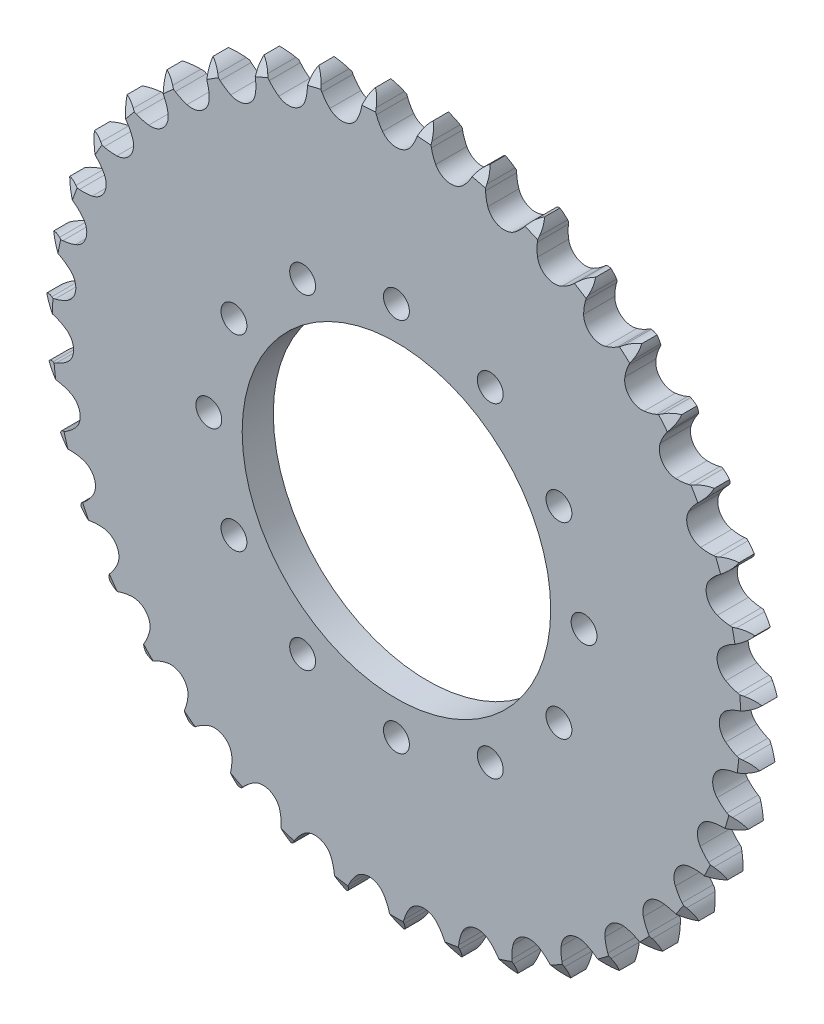
SolidWorks part; units mm, degrees
material "7075-T6 (SN)"
ref_plane "Front Plane" through (0, 0, 0) normal (0, 0, 1) x (1, 0, 0)
ref_plane "Top Plane" through (0, 0, 0) normal (0, 1, 0) x (1, 0, 0)
ref_plane "Right Plane" through (0, 0, 0) normal (1, 0, 0) x (0, 0, -1)
sketch "Work Sketch" plane through (0, 0, 0) normal (0, 0, 1) x (1, 0, 0)
  line L0 (0, 0) -> (0, 160.4542) construction
  line L1 (-112.0919, 78.9148) -> (87.2579, 78.9148) construction
  line L2 (5.102, 120.8822) -> (5.102, 112.9699) construction
  line L3 (-12.8497, 82.6953) -> (16.7256, 82.6953) construction
  line L4 (5.102, 82.6953) -> (-6.0879, 74.4036) construction
  line L5 (5.102, 82.6953) -> (-4.6505, 79.1506) construction
  line L6 (-4.6505, 79.1506) -> (-6.8863, 85.3019)
  line L7 (-11.5114, 78.0206) -> (-7.1525, 78.0206) construction
  line L8 (-11.0765, 124.7602) -> (-11.0765, 110.2345) construction
  line L9 (0, 0) -> (-3.4402, 42.6146) construction
  circle A0 centre (0, 0) radius 78.9148
  circle A1 centre (0, 78.9148) radius 4.0088
  arc A2 (-4.6505, 79.1506) -> (-3.2209, 76.5281) centre (5.0804, 82.7541) ccw
  circle A3 centre (-11.0765, 78.0206) radius 6.4254
  point P23 (-3.2209, 76.5281)
  dimension "D1" = 157.8295
  dimension "D8" = 10.3767
  dimension "D2" = 8.0177
  dimension "D3" = 5.102
  dimension "D4" = 3.7806
  dimension "D5" = 36.538
  dimension "D6" = 16.564
  dimension "D7" = 10.3767
  dimension "D9" = 0.8942
  dimension "D10" = 11.0765
  dimension "D11" = 4.615
sketch "Teeth Sketch" plane through (0, 0, 0) normal (0, 0, 1) x (1, 0, 0)
  line L0 (5.0376, 80.2155) -> (4.6505, 79.1506)
  line L1 (-7.4865, 92.7372) -> (-4.7839, 59.2593) construction
  line L2 (0, 0) -> (-10.9133, 132.3061) construction
  line L3 (7.8951, 79.9848) -> (8.1063, 78.8717)
  line L4 (16093.3137, -199351.4616) -> (-16096.7539, 199394.0762) construction
  line L5 (0, 146.3285) -> (0, 56.9858) construction
  line L6 (17.8398, 78.3686) -> (17.287, 77.3797)
  line L7 (0, -200000) -> (0, 200160.4542) construction
  line L8 (20.6234, 77.6826) -> (20.6533, 76.5499)
  line L9 (-4.6505, 79.1506) -> (-6.8863, 85.3019) construction
  line L10 (44.1616, 67.154) -> (43.8313, 66.0702)
  line L11 (-5.0376, 80.2155) -> (-4.6505, 79.1506)
  line L12 (30.18, 74.4921) -> (29.4757, 73.6046)
  line L13 (32.8175, 73.3684) -> (32.6653, 72.2456)
  line L14 (41.7385, 68.6862) -> (40.901, 67.9232)
  line L15 (52.2161, 61.1014) -> (51.267, 60.4826)
  line L16 (54.362, 59.2003) -> (53.8621, 58.1836)
  line L17 (61.3413, 51.9341) -> (60.3052, 51.4756)
  line L18 (63.1544, 49.7134) -> (62.4979, 48.79)
  line L19 (68.8777, 41.4218) -> (67.7815, 41.1354)
  line L20 (70.3112, 38.939) -> (69.515, 38.1328)
  line L21 (74.6303, 29.8366) -> (73.5023, 29.7298)
  line L22 (75.6469, 27.156) -> (74.7318, 26.488)
  line L23 (78.45, 17.4787) -> (77.3195, 17.5542)
  line L24 (79.0234, 14.6698) -> (78.013, 14.1572)
  line L25 (80.2378, 4.6681) -> (79.1341, 4.9239)
  line L26 (80.3533, 1.8035) -> (79.2737, 1.4597)
  line L27 (79.9476, -8.2634) -> (78.8992, -7.8338)
  line L28 (79.602, -11.1094) -> (78.4813, -11.2756)
  line L29 (77.5867, -20.9809) -> (76.6208, -20.3887)
  line L30 (76.7891, -23.7346) -> (75.6562, -23.7189)
  line L31 (73.2164, -33.155) -> (72.358, -32.4155)
  line L32 (71.9874, -35.7451) -> (70.8717, -35.5478)
  line L33 (66.9499, -44.4704) -> (66.2212, -43.6028)
  line L34 (65.3213, -46.8298) -> (64.2517, -46.4561)
  line L35 (58.9493, -54.634) -> (58.3693, -53.6608)
  line L36 (56.9634, -56.7016) -> (55.9676, -56.1612)
  line L37 (49.422, -63.3827) -> (49.0056, -62.329)
  line L38 (47.1301, -65.1049) -> (46.2339, -64.4118)
  line L39 (38.6147, -70.4897) -> (38.3727, -69.3829)
  line L40 (36.0763, -71.822) -> (35.3028, -70.9941)
  line L41 (26.8073, -75.7712) -> (26.746, -74.6398)
  line L42 (24.088, -76.679) -> (23.4574, -75.7377)
  line L43 (14.3056, -79.0901) -> (14.4266, -77.9636)
  line L44 (11.4759, -79.55) -> (11.0044, -78.5198)
  line L45 (1.4334, -80.3607) -> (1.7335, -79.2682)
  line L46 (-1.4334, -80.3607) -> (-1.7335, -79.2682)
  line L47 (-11.4759, -79.55) -> (-11.0044, -78.5198)
  line L48 (-14.3056, -79.0901) -> (-14.4266, -77.9636)
  line L49 (-24.088, -76.679) -> (-23.4574, -75.7377)
  line L50 (-26.8073, -75.7712) -> (-26.746, -74.6398)
  line L51 (-36.0763, -71.822) -> (-35.3028, -70.9941)
  line L52 (-38.6147, -70.4897) -> (-38.3727, -69.3829)
  line L53 (-47.1301, -65.1049) -> (-46.2339, -64.4118)
  line L54 (-49.422, -63.3827) -> (-49.0056, -62.329)
  line L55 (-56.9634, -56.7016) -> (-55.9676, -56.1612)
  line L56 (-58.9493, -54.634) -> (-58.3693, -53.6608)
  line L57 (-65.3213, -46.8298) -> (-64.2517, -46.4561)
  line L58 (-66.9499, -44.4704) -> (-66.2212, -43.6028)
  line L59 (-71.9874, -35.7451) -> (-70.8717, -35.5478)
  line L60 (-73.2164, -33.155) -> (-72.358, -32.4155)
  line L61 (-76.7891, -23.7346) -> (-75.6562, -23.7189)
  line L62 (-77.5867, -20.9809) -> (-76.6208, -20.3887)
  line L63 (-79.602, -11.1094) -> (-78.4813, -11.2756)
  line L64 (-79.9476, -8.2634) -> (-78.8992, -7.8338)
  line L65 (-80.3533, 1.8035) -> (-79.2737, 1.4597)
  line L66 (-80.2378, 4.6681) -> (-79.1341, 4.9239)
  line L67 (-79.0234, 14.6698) -> (-78.013, 14.1572)
  line L68 (-78.45, 17.4787) -> (-77.3195, 17.5542)
  line L69 (-75.6469, 27.156) -> (-74.7318, 26.488)
  line L70 (-74.6303, 29.8366) -> (-73.5023, 29.7298)
  line L71 (-70.3112, 38.939) -> (-69.515, 38.1328)
  line L72 (-68.8777, 41.4218) -> (-67.7815, 41.1354)
  line L73 (-63.1544, 49.7134) -> (-62.4979, 48.79)
  line L74 (-61.3413, 51.9341) -> (-60.3052, 51.4756)
  line L75 (-54.362, 59.2003) -> (-53.8621, 58.1836)
  line L76 (-52.2161, 61.1014) -> (-51.267, 60.4826)
  line L77 (-44.1616, 67.154) -> (-43.8313, 66.0702)
  line L78 (-41.7385, 68.6862) -> (-40.901, 67.9232)
  line L79 (-32.8175, 73.3684) -> (-32.6653, 72.2456)
  line L80 (-30.18, 74.4921) -> (-29.4757, 73.6046)
  line L81 (-20.6234, 77.6826) -> (-20.6533, 76.5499)
  line L82 (-17.8398, 78.3686) -> (-17.287, 77.3797)
  line L83 (-7.8951, 79.9848) -> (-8.1063, 78.8717)
  arc A0 (-6.8336, 82.8459) -> (-5.0376, 80.2155) centre (-11.0765, 78.0206) cw
  circle A1 centre (-11.0765, 78.0206) radius 6.4254 construction
  arc A2 (-3.2209, 76.5281) -> (-4.6505, 79.1506) centre (5.0804, 82.7541) cw
  arc A3 (-4.6505, 79.1506) -> (-3.2209, 76.5281) centre (5.0804, 82.7541) ccw construction
  circle A4 centre (0, 78.9148) radius 4.0088 construction
  arc A5 (-3.2209, 76.5281) -> (3.2209, 76.5281) centre (0, 78.9148) ccw
  arc A6 (3.2209, 76.5281) -> (4.6505, 79.1506) centre (-5.0804, 82.7541) ccw
  arc A7 (6.8336, 82.8459) -> (5.0376, 80.2155) centre (11.0765, 78.0206) ccw
  arc A8 (6.5443, 82.8692) -> (7.8951, 79.9848) centre (1.5824, 78.787) cw
  arc A9 (9.0967, 76.0537) -> (8.1063, 78.8717) centre (18.2893, 80.8676) cw
  arc A10 (9.0967, 76.0537) -> (15.4552, 75.0204) centre (12.6588, 77.8928) ccw
  arc A11 (15.4552, 75.0204) -> (17.287, 77.3797) centre (8.2601, 82.4975) ccw
  arc A12 (20.0345, 80.6769) -> (17.8398, 78.3686) centre (23.4484, 75.2334) ccw
  arc A13 (19.7528, 80.7463) -> (20.6234, 77.6826) centre (14.2002, 77.5129) cw
  arc A14 (21.1788, 73.6096) -> (20.6533, 76.5499) centre (31.0245, 76.8865) cw
  arc A15 (21.1788, 73.6096) -> (27.2892, 71.5697) centre (24.9898, 74.8535) ccw
  arc A16 (27.2892, 71.5697) -> (29.4757, 73.6046) centre (21.3867, 80.1041) ccw
  arc A17 (32.7165, 76.4184) -> (30.18, 74.4921) centre (35.2131, 70.4978) ccw
  arc A18 (32.4496, 76.5321) -> (32.8175, 73.3684) centre (26.4502, 74.2313) cw
  arc A19 (32.7124, 69.2591) -> (32.6653, 72.2456) centre (42.9562, 70.9142) cw
  arc A20 (32.7124, 69.2591) -> (38.4163, 66.2654) centre (36.6735, 69.8756) ccw
  arc A21 (38.4163, 66.2654) -> (40.901, 67.9232) centre (33.9593, 75.6361) ccw
  arc A22 (44.5512, 70.1807) -> (41.7385, 68.6862) centre (46.0657, 63.9363) ccw
  arc A23 (44.306, 70.3358) -> (44.1616, 67.154) centre (38.0153, 69.0271) cw
  arc A24 (43.3987, 63.1147) -> (43.8313, 66.0702) centre (53.7754, 63.1052) cw
  arc A25 (43.3987, 63.1147) -> (48.5486, 59.2448) centre (47.4074, 63.0878) ccw
  arc A26 (48.5486, 59.2448) -> (51.267, 60.4826) centre (45.6524, 69.2092) ccw
  arc A27 (55.2321, 62.1253) -> (52.2161, 61.1014) centre (55.7253, 55.7189) ccw
  arc A28 (55.0149, 62.3178) -> (54.362, 59.2003) centre (48.5957, 62.0351) cw
  arc A29 (52.961, 55.3358) -> (53.8621, 58.1836) centre (63.2018, 53.6618) cw
  arc A30 (52.961, 55.3358) -> (57.4234, 50.6899) centre (56.9135, 54.6662) ccw
  arc A31 (57.4234, 50.6899) -> (60.3052, 51.4756) centre (56.1632, 60.9898) ccw
  arc A32 (64.4824, 52.461) -> (61.3413, 51.9341) centre (63.9416, 46.0584) ccw
  arc A33 (64.2989, 52.6858) -> (63.1544, 49.7134) centre (57.9175, 53.4365) cw
  arc A34 (61.1517, 46.1237) -> (62.4979, 48.79) centre (70.9913, 42.8287) cw
  arc A35 (61.1517, 46.1237) -> (64.811, 40.8221) centre (64.9456, 44.8287) ccw
  arc A36 (64.811, 40.8221) -> (67.7815, 41.1354) centre (65.2193, 51.1908) ccw
  arc A37 (72.0627, 41.4379) -> (68.8777, 41.4218) centre (70.5018, 35.205) ccw
  arc A38 (71.9177, 41.6892) -> (70.3112, 38.939) centre (65.7393, 43.4539) cw
  arc A39 (67.7585, 35.717) -> (69.515, 38.1328) centre (76.9422, 30.8862) cw
  arc A40 (67.7585, 35.717) -> (70.5201, 29.8971) centre (71.2956, 33.8302) ccw
  arc A41 (70.5201, 29.8971) -> (73.5023, 29.7298) centre (72.5864, 40.0659) ccw
  arc A42 (77.7767, 29.3416) -> (74.6303, 29.8366) centre (75.2361, 23.4398) ccw
  arc A43 (77.6738, 29.6129) -> (75.6469, 27.156) centre (71.8585, 32.3458) cw
  arc A44 (72.6105, 24.3852) -> (74.7318, 26.488) centre (80.9003, 18.1439) cw
  arc A45 (72.6105, 24.3852) -> (74.4027, 18.1977) centre (75.7991, 21.9555) ccw
  arc A46 (74.4027, 18.1977) -> (77.3195, 17.5542) centre (78.0734, 27.9034) ccw
  arc A47 (81.4762, 16.4854) -> (78.45, 17.4787) centre (78.0218, 11.0675) ccw
  arc A48 (81.4182, 16.7697) -> (79.0234, 14.6698) centre (76.1166, 20.4) cw
  arc A49 (75.5818, 12.4219) -> (78.013, 14.1572) centre (82.7631, 4.9316) cw
  arc A50 (75.5818, 12.4219) -> (76.3583, 6.027) centre (78.3394, 9.5121) ccw
  arc A51 (76.3583, 6.027) -> (79.1341, 4.9239) centre (81.5384, 15.0182) ccw
  arc A52 (83.0656, 3.2022) -> (80.2378, 4.6681) centre (78.7868, -1.5914) ccw
  arc A53 (83.0539, 3.4922) -> (80.3533, 1.8035) centre (78.4033, 7.9259) cw
  arc A54 (76.5957, 0.1368) -> (79.2737, 1.4597) centre (82.4825, -8.4084) cw
  arc A55 (76.5957, 0.1368) -> (76.3363, -6.2998) centre (78.8508, -3.1776) ccw
  arc A56 (76.3363, -6.2998) -> (78.8992, -7.8338) centre (82.8916, 1.7441) ccw
  arc A57 (82.5035, -10.1639) -> (79.9476, -8.2634) centre (77.5113, -14.2091) ccw
  arc A58 (82.5385, -9.8758) -> (79.602, -11.1094) centre (78.6594, -4.7535) cw
  arc A59 (75.6257, -12.1517) -> (78.4813, -11.2756) centre (80.0655, -21.5307) cw
  arc A60 (75.6257, -12.1517) -> (74.3372, -18.4634) centre (77.3199, -15.785) ccw
  arc A61 (74.3372, -18.4634) -> (76.6208, -20.3887) centre (82.0979, -11.5753) ccw
  arc A62 (79.8047, -23.2668) -> (77.5867, -20.9809) centre (74.2283, -26.4587) ccw
  arc A63 (79.8855, -22.9881) -> (76.7891, -23.7346) centre (76.8783, -17.3098) cw
  arc A64 (72.6971, -24.1256) -> (75.6562, -23.7189) centre (75.5749, -34.0953) cw
  arc A65 (72.6971, -24.1256) -> (70.4128, -30.1488) centre (73.7866, -27.9836) ccw
  arc A66 (70.4128, -30.1488) -> (72.358, -32.4155) centre (79.178, -24.5948) ccw
  arc A67 (75.039, -35.7671) -> (73.2164, -33.155) centre (69.0227, -38.0232) ccw
  arc A68 (75.1634, -35.5049) -> (71.9874, -35.7451) centre (73.106, -29.4178) cw
  arc A69 (67.8857, -35.4746) -> (70.8717, -35.5478) centre (69.127, -45.7768) cw
  arc A70 (67.8857, -35.4746) -> (64.6648, -41.0534) centre (68.3422, -39.4574) ccw
  arc A71 (64.6648, -41.0534) -> (66.2212, -43.6028) centre (74.2074, -36.9773) ccw
  arc A72 (68.3299, -47.341) -> (66.9499, -44.4704) centre (62.0296, -48.6028) ccw
  arc A73 (68.4947, -47.1022) -> (65.3213, -46.8298) centre (67.4404, -40.7639) cw
  arc A74 (61.3161, -45.9049) -> (64.2517, -46.4561) centre (60.8887, -56.2728) cw
  arc A75 (61.3161, -45.9049) -> (57.2419, -50.8948) centre (61.1278, -49.9093) ccw
  arc A76 (57.2419, -50.8948) -> (58.3693, -53.6608) centre (67.3148, -48.4022) ccw
  arc A77 (59.851, -57.6888) -> (58.9493, -54.634) centre (53.4299, -57.9236) ccw
  arc A78 (60.052, -57.4796) -> (56.9634, -56.7016) centre (60.0281, -51.0542) cw
  arc A79 (53.1584, -55.1462) -> (55.9676, -56.1612) centre (51.0734, -65.3113) cw
  arc A80 (53.1584, -55.1462) -> (48.3366, -59.4179) centre (52.3302, -59.0685) ccw
  arc A81 (48.3366, -59.4179) -> (49.0056, -62.329) centre (58.6789, -58.5735) ccw
  arc A82 (49.822, -66.5425) -> (49.422, -63.3827) centre (43.4464, -65.7443) ccw
  arc A83 (50.054, -66.3682) -> (47.1301, -65.1049) centre (51.0611, -60.0222) cw
  arc A84 (43.6239, -62.9593) -> (46.2339, -64.4118) centre (39.9354, -72.6583) cw
  arc A85 (43.6239, -62.9593) -> (38.1793, -66.4022) centre (42.1772, -66.698) ccw
  arc A86 (38.1793, -66.4022) -> (38.3727, -69.3829) centre (48.5231, -67.2277) ccw
  arc A87 (38.5026, -73.6728) -> (38.6147, -70.4897) centre (32.3376, -71.8622) ccw
  arc A88 (38.7596, -73.538) -> (36.0763, -71.822) centre (40.7716, -67.4357) cw
  arc A89 (32.9596, -69.1417) -> (35.3028, -70.9941) centre (27.763, -78.1234) cw
  arc A90 (32.9596, -69.1417) -> (27.0333, -71.6667) centre (30.932, -72.6) ccw
  arc A91 (27.0333, -71.6667) -> (26.746, -74.6398) centre (37.1107, -74.1408) ccw
  arc A92 (26.1861, -78.8951) -> (26.8073, -75.7712) centre (20.3913, -76.1189) ccw
  arc A93 (26.4613, -78.8032) -> (24.088, -76.679) centre (29.4261, -73.1027) cw
  arc A94 (21.4417, -73.5335) -> (23.4574, -75.7377) centre (14.8716, -81.5653) cw
  arc A95 (21.4417, -73.5335) -> (15.187, -75.0751) centre (18.8855, -76.6216) ccw
  arc A96 (15.187, -75.0751) -> (14.4266, -77.9636) centre (24.7371, -79.1336) ccw
  arc A97 (13.1913, -82.0739) -> (14.3056, -79.0901) centre (7.9169, -78.4042) ccw
  arc A98 (13.4777, -82.0274) -> (11.4759, -79.55) centre (17.3186, -76.8763) cw
  arc A99 (9.3684, -76.0207) -> (11.0044, -78.5198) centre (1.595, -82.8946) cw
  arc A100 (9.3684, -76.0207) -> (2.9475, -76.5391) centre (6.35, -78.6589) ccw
  arc A101 (2.9475, -76.5391) -> (1.7335, -79.2682) centre (11.7228, -82.077) ccw
  arc A102 (-0.1451, -83.1271) -> (1.4334, -80.3607) centre (-4.7625, -78.6589) ccw
  arc A103 (0.1451, -83.1271) -> (-1.4334, -80.3607) centre (4.7625, -78.6589) cw
  arc A104 (-2.9475, -76.5391) -> (-1.7335, -79.2682) centre (-11.7228, -82.077) cw
  arc A105 (-2.9475, -76.5391) -> (-9.3684, -76.0207) centre (-6.35, -78.6589) ccw
  arc A106 (-9.3684, -76.0207) -> (-11.0044, -78.5198) centre (-1.595, -82.8946) ccw
  arc A107 (-13.4777, -82.0274) -> (-11.4759, -79.55) centre (-17.3186, -76.8763) ccw
  arc A108 (-13.1913, -82.0739) -> (-14.3056, -79.0901) centre (-7.9169, -78.4042) cw
  arc A109 (-15.187, -75.0751) -> (-14.4266, -77.9636) centre (-24.7371, -79.1336) cw
  arc A110 (-15.187, -75.0751) -> (-21.4417, -73.5335) centre (-18.8855, -76.6216) ccw
  arc A111 (-21.4417, -73.5335) -> (-23.4574, -75.7377) centre (-14.8716, -81.5653) ccw
  arc A112 (-26.4613, -78.8032) -> (-24.088, -76.679) centre (-29.4261, -73.1027) ccw
  arc A113 (-26.1861, -78.8951) -> (-26.8073, -75.7712) centre (-20.3913, -76.1189) cw
  arc A114 (-27.0333, -71.6667) -> (-26.746, -74.6398) centre (-37.1107, -74.1408) cw
  arc A115 (-27.0333, -71.6667) -> (-32.9596, -69.1417) centre (-30.932, -72.6) ccw
  arc A116 (-32.9596, -69.1417) -> (-35.3028, -70.9941) centre (-27.763, -78.1234) ccw
  arc A117 (-38.7596, -73.538) -> (-36.0763, -71.822) centre (-40.7716, -67.4357) ccw
  arc A118 (-38.5026, -73.6728) -> (-38.6147, -70.4897) centre (-32.3376, -71.8622) cw
  arc A119 (-38.1793, -66.4022) -> (-38.3727, -69.3829) centre (-48.5231, -67.2277) cw
  arc A120 (-38.1793, -66.4022) -> (-43.6239, -62.9593) centre (-42.1772, -66.698) ccw
  arc A121 (-43.6239, -62.9593) -> (-46.2339, -64.4118) centre (-39.9354, -72.6583) ccw
  arc A122 (-50.054, -66.3682) -> (-47.1301, -65.1049) centre (-51.0611, -60.0222) ccw
  arc A123 (-49.822, -66.5425) -> (-49.422, -63.3827) centre (-43.4464, -65.7443) cw
  arc A124 (-48.3366, -59.4179) -> (-49.0056, -62.329) centre (-58.6789, -58.5735) cw
  arc A125 (-48.3366, -59.4179) -> (-53.1584, -55.1462) centre (-52.3302, -59.0685) ccw
  arc A126 (-53.1584, -55.1462) -> (-55.9676, -56.1612) centre (-51.0734, -65.3113) ccw
  arc A127 (-60.052, -57.4796) -> (-56.9634, -56.7016) centre (-60.0281, -51.0542) ccw
  arc A128 (-59.851, -57.6888) -> (-58.9493, -54.634) centre (-53.4299, -57.9236) cw
  arc A129 (-57.2419, -50.8948) -> (-58.3693, -53.6608) centre (-67.3148, -48.4022) cw
  arc A130 (-57.2419, -50.8948) -> (-61.3161, -45.9049) centre (-61.1278, -49.9093) ccw
  arc A131 (-61.3161, -45.9049) -> (-64.2517, -46.4561) centre (-60.8887, -56.2728) ccw
  arc A132 (-68.4947, -47.1022) -> (-65.3213, -46.8298) centre (-67.4404, -40.7639) ccw
  arc A133 (-68.3299, -47.341) -> (-66.9499, -44.4704) centre (-62.0296, -48.6028) cw
  arc A134 (-64.6648, -41.0534) -> (-66.2212, -43.6028) centre (-74.2074, -36.9773) cw
  arc A135 (-64.6648, -41.0534) -> (-67.8857, -35.4746) centre (-68.3422, -39.4574) ccw
  arc A136 (-67.8857, -35.4746) -> (-70.8717, -35.5478) centre (-69.127, -45.7768) ccw
  arc A137 (-75.1634, -35.5049) -> (-71.9874, -35.7451) centre (-73.106, -29.4178) ccw
  arc A138 (-75.039, -35.7671) -> (-73.2164, -33.155) centre (-69.0227, -38.0232) cw
  arc A139 (-70.4128, -30.1488) -> (-72.358, -32.4155) centre (-79.178, -24.5948) cw
  arc A140 (-70.4128, -30.1488) -> (-72.6971, -24.1256) centre (-73.7866, -27.9836) ccw
  arc A141 (-72.6971, -24.1256) -> (-75.6562, -23.7189) centre (-75.5749, -34.0953) ccw
  arc A142 (-79.8855, -22.9881) -> (-76.7891, -23.7346) centre (-76.8783, -17.3098) ccw
  arc A143 (-79.8047, -23.2668) -> (-77.5867, -20.9809) centre (-74.2283, -26.4587) cw
  arc A144 (-74.3372, -18.4634) -> (-76.6208, -20.3887) centre (-82.0979, -11.5753) cw
  arc A145 (-74.3372, -18.4634) -> (-75.6257, -12.1517) centre (-77.3199, -15.785) ccw
  arc A146 (-75.6257, -12.1517) -> (-78.4813, -11.2756) centre (-80.0655, -21.5307) ccw
  arc A147 (-82.5385, -9.8758) -> (-79.602, -11.1094) centre (-78.6594, -4.7535) ccw
  arc A148 (-82.5035, -10.1639) -> (-79.9476, -8.2634) centre (-77.5113, -14.2091) cw
  arc A149 (-76.3363, -6.2998) -> (-78.8992, -7.8338) centre (-82.8916, 1.7441) cw
  arc A150 (-76.3363, -6.2998) -> (-76.5957, 0.1368) centre (-78.8508, -3.1776) ccw
  arc A151 (-76.5957, 0.1368) -> (-79.2737, 1.4597) centre (-82.4825, -8.4084) ccw
  arc A152 (-83.0539, 3.4922) -> (-80.3533, 1.8035) centre (-78.4033, 7.9259) ccw
  arc A153 (-83.0656, 3.2022) -> (-80.2378, 4.6681) centre (-78.7868, -1.5914) cw
  arc A154 (-76.3583, 6.027) -> (-79.1341, 4.9239) centre (-81.5384, 15.0182) cw
  arc A155 (-76.3583, 6.027) -> (-75.5818, 12.4219) centre (-78.3394, 9.5121) ccw
  arc A156 (-75.5818, 12.4219) -> (-78.013, 14.1572) centre (-82.7631, 4.9316) ccw
  arc A157 (-81.4182, 16.7697) -> (-79.0234, 14.6698) centre (-76.1166, 20.4) ccw
  arc A158 (-81.4762, 16.4854) -> (-78.45, 17.4787) centre (-78.0218, 11.0675) cw
  arc A159 (-74.4027, 18.1977) -> (-77.3195, 17.5542) centre (-78.0734, 27.9034) cw
  arc A160 (-74.4027, 18.1977) -> (-72.6105, 24.3852) centre (-75.7991, 21.9555) ccw
  arc A161 (-72.6105, 24.3852) -> (-74.7318, 26.488) centre (-80.9003, 18.1439) ccw
  arc A162 (-77.6738, 29.6129) -> (-75.6469, 27.156) centre (-71.8585, 32.3458) ccw
  arc A163 (-77.7767, 29.3416) -> (-74.6303, 29.8366) centre (-75.2361, 23.4398) cw
  arc A164 (-70.5201, 29.8971) -> (-73.5023, 29.7298) centre (-72.5864, 40.0659) cw
  arc A165 (-70.5201, 29.8971) -> (-67.7585, 35.717) centre (-71.2956, 33.8302) ccw
  arc A166 (-67.7585, 35.717) -> (-69.515, 38.1328) centre (-76.9422, 30.8862) ccw
  arc A167 (-71.9177, 41.6892) -> (-70.3112, 38.939) centre (-65.7393, 43.4539) ccw
  arc A168 (-72.0627, 41.4379) -> (-68.8777, 41.4218) centre (-70.5018, 35.205) cw
  arc A169 (-64.811, 40.8221) -> (-67.7815, 41.1354) centre (-65.2193, 51.1908) cw
  arc A170 (-64.811, 40.8221) -> (-61.1517, 46.1237) centre (-64.9456, 44.8287) ccw
  arc A171 (-61.1517, 46.1237) -> (-62.4979, 48.79) centre (-70.9913, 42.8287) ccw
  arc A172 (-64.2989, 52.6858) -> (-63.1544, 49.7134) centre (-57.9175, 53.4365) ccw
  arc A173 (-64.4824, 52.461) -> (-61.3413, 51.9341) centre (-63.9416, 46.0584) cw
  arc A174 (-57.4234, 50.6899) -> (-60.3052, 51.4756) centre (-56.1632, 60.9898) cw
  arc A175 (-57.4234, 50.6899) -> (-52.961, 55.3358) centre (-56.9135, 54.6662) ccw
  arc A176 (-52.961, 55.3358) -> (-53.8621, 58.1836) centre (-63.2018, 53.6618) ccw
  arc A177 (-55.0149, 62.3178) -> (-54.362, 59.2003) centre (-48.5957, 62.0351) ccw
  arc A178 (-55.2321, 62.1253) -> (-52.2161, 61.1014) centre (-55.7253, 55.7189) cw
  arc A179 (-48.5486, 59.2448) -> (-51.267, 60.4826) centre (-45.6524, 69.2092) cw
  arc A180 (-48.5486, 59.2448) -> (-43.3987, 63.1147) centre (-47.4074, 63.0878) ccw
  arc A181 (-43.3987, 63.1147) -> (-43.8313, 66.0702) centre (-53.7754, 63.1052) ccw
  arc A182 (-44.306, 70.3358) -> (-44.1616, 67.154) centre (-38.0153, 69.0271) ccw
  arc A183 (-44.5512, 70.1807) -> (-41.7385, 68.6862) centre (-46.0657, 63.9363) cw
  arc A184 (-38.4163, 66.2654) -> (-40.901, 67.9232) centre (-33.9593, 75.6361) cw
  arc A185 (-38.4163, 66.2654) -> (-32.7124, 69.2591) centre (-36.6735, 69.8756) ccw
  arc A186 (-32.7124, 69.2591) -> (-32.6653, 72.2456) centre (-42.9562, 70.9142) ccw
  arc A187 (-32.4496, 76.5321) -> (-32.8175, 73.3684) centre (-26.4502, 74.2313) ccw
  arc A188 (-32.7165, 76.4184) -> (-30.18, 74.4921) centre (-35.2131, 70.4978) cw
  arc A189 (-27.2892, 71.5697) -> (-29.4757, 73.6046) centre (-21.3867, 80.1041) cw
  arc A190 (-27.2892, 71.5697) -> (-21.1788, 73.6096) centre (-24.9898, 74.8535) ccw
  arc A191 (-21.1788, 73.6096) -> (-20.6533, 76.5499) centre (-31.0245, 76.8865) ccw
  arc A192 (-19.7528, 80.7463) -> (-20.6234, 77.6826) centre (-14.2002, 77.5129) ccw
  arc A193 (-20.0345, 80.6769) -> (-17.8398, 78.3686) centre (-23.4484, 75.2334) cw
  arc A194 (-15.4552, 75.0204) -> (-17.287, 77.3797) centre (-8.2601, 82.4975) cw
  arc A195 (-15.4552, 75.0204) -> (-9.0967, 76.0537) centre (-12.6588, 77.8928) ccw
  arc A196 (-9.0967, 76.0537) -> (-8.1063, 78.8717) centre (-18.2893, 80.8676) ccw
  arc A197 (-6.5443, 82.8692) -> (-7.8951, 79.9848) centre (-1.5824, 78.787) ccw
  point P77 (0, 0)
  dimension "D1" = 4.615
  dimension "D2" = 4.715
  dimension "D3" = 39
extrude "Extrusion" add sketch "Teeth Sketch" along normal blind 7.2136 contours A0 region at (0, 0, 0)
sketch "Sketch1" plane through (0, 0, 0) normal (0, 0, -1) x (-1, 0, 0)
  circle A0 centre (0, 0) radius 78.9443
  circle A1 centre (0, 0) radius 35.7643
  dimension "D1" = 43.18
extrude "Cut-Extrude" cut sketch "Sketch1" against normal through all both and the other way through all contours A1
ref_axis "Axis1" [suppressed] through (0, 0, 7.2136) along (0, 0, -1)
ref_plane "Sprocket Center Plane" through (0, 0, 3.6068) normal (0, 0, 1) x (1, 0, 0)
sketch "Pitch Circle" plane through (0, 0, 3.6068) normal (0, 0, -1) x (-1, 0, 0)
  circle A0 centre (0, 0) radius 82.9531 construction
  dimension "D1" = 165.9063
sketch "Chain Pitch Circle" plane through (0, 0, 0) normal (0, 0, -1) x (-1, 0, 0)
  circle A0 centre (0, 0) radius 82.9531 construction
  dimension "D1" = 165.9063
ref_plane "Center Plane" through (0, 0, 3.6068) normal (0, 0, 1) x (1, 0, 0)
hole_wizard "Ø6.0mm Dowel Hole1" positions "Sketch7" profile "Sketch8" hole size "Ø6.0" standard "ANSI Metric" end condition through all
sketch "Sketch7" plane through (0, 0, 7.2136) normal (0, 0, 1) x (1, 0, 0)
  point P0 (-43.5, 0)
  dimension "D1" = 43.5
sketch "Sketch8" plane through (-43.5, 0, 7.2136) normal (1, 0, 0) x (0, -1, 0)
  line L0 (0, 0) -> (0, 7.2136)
  line L1 (0, 7.2136) -> (3, 7.2136)
  line L2 (3, 7.2136) -> (3, 0)
  line L5 (3, 0) -> (0, 0)
  line L11 (0, -6.35) -> (0, 107.95) construction
  dimension "Thru Hole Dia." = 6
  dimension "Thru Hole Depth" = 7.2136
pattern_circular "CirPattern1" count 12 over 360 about axis through (0, 0, 7.2136) along (0, 0, -1) of "Ø6.0mm Dowel Hole1" reverse direction yes
sketch "Sketch5" plane through (0, 0, 0) normal (1, 0, 0) x (0, 0, -1)
  line L0 (-1.8288, -82.9722) -> (-5.3848, -82.9722)
  line L3 (-5.3848, -79.7786) -> (-7.2136, -79.7786)
  line L5 (-7.2136, -79.7786) -> (-7.2136, -82.9722)
  line L6 (-7.2136, -82.9722) -> (-5.3848, -82.9722)
  line L7 (-7.2136, -82.9722) -> (0, -82.9722) construction
  line L8 (-7.2136, -82.9722) -> (0, -82.9722)
  line L9 (-5.3848, -82.9722) -> (-7.2136, -79.7786)
  line L10 (-5.3848, -79.7786) -> (-5.3848, -82.9722)
  point P5 (-3.6068, -82.9722)
  dimension "D1" = 3.556
  dimension "D2" = 3.1936
  dimension "D3" = 1.8288
revolve "Cut-Revolve1" cut sketch "Sketch5" angle 360 about axis through (0, 0, 7.2136) along (0, 0, -1) region at (0, -81.9076, 6.604)
mirror "Mirror1" about plane through (0, 0, 3.6068) normal (0, 0, 1) of "Cut-Revolve1"
equation "\"P\"= 0.500'//Chain Pitch"
equation "\"N\"= 39'//Number of Teeth"
equation "\"Dr\"= 5 / 16'//Roller Diameter"
equation "\"Ds\"= 1.0005 * \"Dr\" + 0.003'Seating Curve DIameter"
equation "\"R\"= \"Ds\" / 2"
equation "\"A\"= 35 + 60 / \"N\""
equation "\"B\"= 18 - 56 / \"N\""
equation "\"ac\"= 0.8 * \"Dr\""
equation "\"M\"= 0.8 * \"Dr\" * cos ( 35 + 60 / \"N\" )"
equation "\"T\"= 0.8 * \"Dr\" * sin ( 35 + 60 / \"N\" )"
equation "\"E\"= 1.3025 * \"Dr\" + 0.0015"
equation "\"Chordal Length of Arc xy\"= ( 2.605 * \"Dr\" + 0.003 ) * sin ( 9 - 28 / \"N\" )"
equation "\"yz\"= \"Dr\" * ( 1.4 * sin ( 17 - 64 / \"N\" ) - 0.8 * sin ( 18 - 56 / \"N\" ) )"
equation "\"ab\"= 1.4 * \"Dr\""
equation "\"W\"= 1.4 * \"Dr\" * cos ( 180 / \"N\" )"
equation "\"V\"= 1.4 * \"Dr\" * sin ( 180 / \"N\" )"
equation "\"F\"= \"Dr\" * ( 0.8 * cos ( 18 - 56 / \"N\" ) + 1.4 * cos ( 17 - 64 / \"N\" ) - 1.3025 )"
equation "\"H\"= sqr ( \"F\" ^ 2 - ( 1.4 * \"Dr\" - \"P\" / 2 ) ^ 2 )"
equation "\"S\"= \"P\" / 2 * cos ( 180 / \"N\" ) + \"H\" * sin ( 180 / \"N\" )"
equation "\"PD\"= \"P\" / ( sin ( 180 / \"N\" ) )"
equation "\"D1@Work Sketch\" = \"PD\""
equation "\"D3@Work Sketch\" = \"M\""
equation "\"D4@Work Sketch\" = \"T\""
equation "\"D5@Work Sketch\" = \"A\""
equation "\"D6@Work Sketch\" = \"B\""
equation "\"D7@Work Sketch\" = \"E\""
equation "\"D8@Work Sketch\" = \"E\""
equation "\"D9@Work Sketch\" = \"V\""
equation "\"D10@Work Sketch\" = \"W\""
equation "\"D2@Work Sketch\" = \"R\" * 2"
equation "\"D11@Work Sketch\" = 180 / \"N\""
equation "\"D2@Teeth Sketch\" = 180 / \"N\" + 0.1"
equation "\"D3@Teeth Sketch\" = \"N\""
equation "\"Edge Thickness\"=1.7"
equation "\"D1@Sketch1\"=\"Edge Thickness\""
equation "\"ST\"= 0.284'//Sprocket Thickness"
